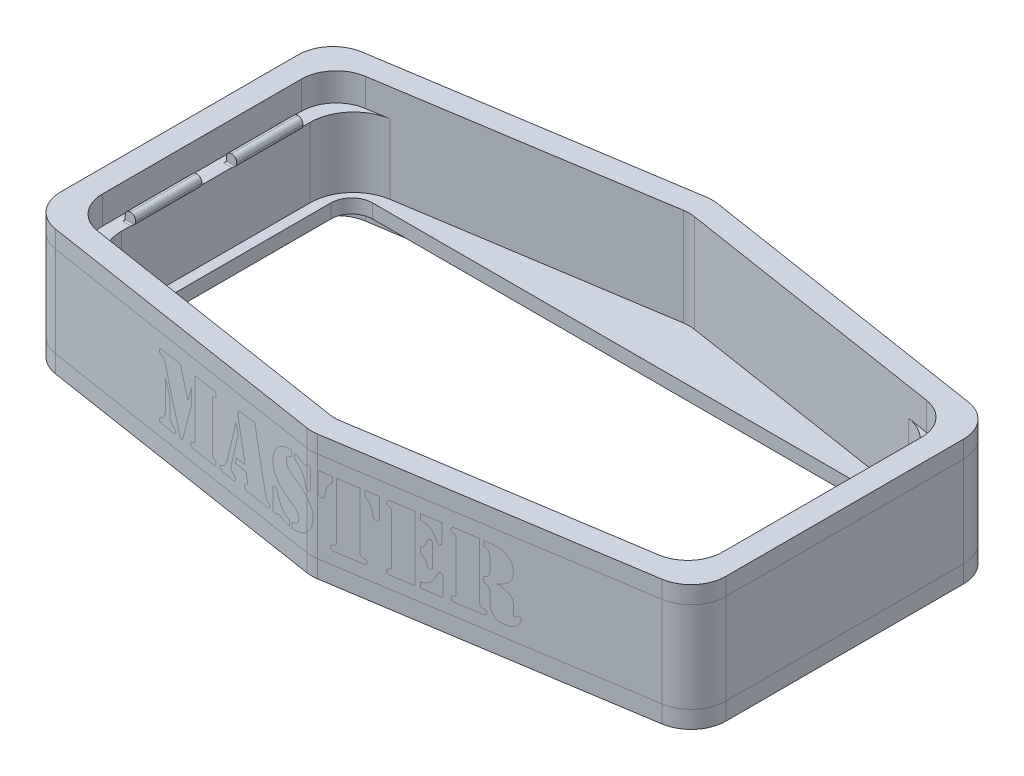
SolidWorks part; units mm, degrees
ref_plane "Front" through (0, 0, 0) normal (0, 0, 1) x (1, 0, 0)
ref_plane "Top" through (0, 0, 0) normal (0, 1, 0) x (1, 0, 0)
ref_plane "Right" through (0, 0, 0) normal (1, 0, 0) x (0, 0, -1)
sketch "Sketch1" plane through (0, 0, 0) normal (0, 1, 0) x (1, 0, 0)
  line L0 (-22.352, 9.2075) -> (0, 12.7) construction
  line L1 (-22.352, -12.7) -> (22.352, -12.7) construction
  line L2 (-22.352, -12.7) -> (-22.352, 12.7) construction
  line L3 (-22.352, 12.7) -> (22.352, 12.7) construction
  line L4 (22.352, -12.7) -> (22.352, 12.7) construction
  line L5 (-22.352, -12.7) -> (22.352, 12.7) construction
  line L6 (-22.352, 12.7) -> (22.352, -12.7) construction
  line L7 (-22.352, -9.2075) -> (22.352, -9.2075) construction
  line L8 (-22.352, -9.2075) -> (-22.352, 9.2075) construction
  line L9 (-22.352, 9.2075) -> (22.352, 9.2075) construction
  line L10 (22.352, -9.2075) -> (22.352, 9.2075) construction
  line L11 (-22.352, -9.2075) -> (22.352, 9.2075) construction
  line L12 (-22.352, 9.2075) -> (22.352, -9.2075) construction
  line L13 (0, 12.7) -> (22.352, 9.2075) construction
  line L14 (22.352, 9.2075) -> (22.352, -9.2075) construction
  line L15 (22.352, -9.2075) -> (0, -12.7) construction
  line L16 (0, -12.7) -> (-22.352, -9.2075) construction
  line L17 (-22.352, -9.2075) -> (-22.352, 9.2075) construction
  line L18 (-22.606, 9.4249) -> (0, 12.9571)
  line L19 (0, 12.9571) -> (22.606, 9.4249)
  line L20 (22.606, 9.4249) -> (22.606, -9.4249)
  line L21 (22.606, -9.4249) -> (0, -12.9571)
  line L22 (0, -12.9571) -> (-22.606, -9.4249)
  line L23 (-22.606, -9.4249) -> (-22.606, 9.4249)
  line L24 (-24.257, 10.838) -> (0, 14.6281)
  line L25 (0, 14.6281) -> (24.257, 10.838)
  line L26 (24.257, 10.838) -> (24.257, -10.838)
  line L27 (24.257, -10.838) -> (0, -14.6281)
  line L28 (0, -14.6281) -> (-24.257, -10.838)
  line L29 (-24.257, -10.838) -> (-24.257, 10.838)
  point P0 (0, 0)
  point P6 (0, 0)
  dimension "D1" = 25.4
  dimension "D2" = 18.415
  dimension "D3" = 44.704
  dimension "D4" = 0.254
  dimension "D5" = 1.651
extrude "Boss-Extrude1" add sketch "Sketch1" along normal blind 9.144
fillet "Fillet1" radius 2.54 12 edges at (0, 4.572, -14.6281) (0, 4.572, 12.9571) (0, 4.572, 14.6281) (0, 4.572, -12.9571) (22.606, 4.572, -9.4249) (22.606, 4.572, 9.4249) (-22.606, 4.572, 9.4249) (-22.606, 4.572, -9.4249) (-24.257, 4.572, -10.838) (24.257, 4.572, -10.838) (24.257, 4.572, 10.838) (-24.257, 4.572, 10.838)
ref_plane "Plane1" through (0, 1.524, 0) normal (0, -1, 0) x (-1, 0, 0)
sketch "Sketch2" plane through (0, 1.524, 0) normal (0, -1, 0) x (-1, 0, 0)
  line L0 (-22.606, -7.251) -> (-22.606, 7.251) construction
  line L1 (-19.304, 9.144) -> (19.304, 9.144)
  line L2 (-20.828, 7.62) -> (-20.828, -7.62)
  line L3 (-19.304, -9.144) -> (19.304, -9.144)
  line L4 (20.828, 7.62) -> (20.828, -7.62)
  line L5 (-0.3921, -12.8958) -> (-20.4581, -9.7605) construction
  line L6 (20.4581, -9.7605) -> (0.3921, -12.8958) construction
  line L7 (22.606, 7.251) -> (22.606, -7.251) construction
  line L8 (0.3921, 12.8958) -> (20.4581, 9.7605) construction
  line L9 (-20.4581, 9.7605) -> (-0.3921, 12.8958) construction
  line L10 (-22.606, -7.251) -> (-22.606, 7.251)
  line L11 (-0.3921, -12.8958) -> (-20.4581, -9.7605)
  line L12 (20.4581, -9.7605) -> (0.3921, -12.8958)
  line L13 (22.606, 7.251) -> (22.606, -7.251)
  line L14 (0.3921, 12.8958) -> (20.4581, 9.7605)
  line L15 (-20.4581, 9.7605) -> (-0.3921, 12.8958)
  arc A0 (-20.828, 7.62) -> (-19.304, 9.144) centre (-19.304, 7.62) cw
  arc A1 (19.304, 9.144) -> (20.828, 7.62) centre (19.304, 7.62) cw
  arc A2 (20.828, -7.62) -> (19.304, -9.144) centre (19.304, -7.62) cw
  arc A3 (-20.828, -7.62) -> (-19.304, -9.144) centre (-19.304, -7.62) ccw
  arc A4 (-20.4581, 9.7605) -> (-22.606, 7.251) centre (-20.066, 7.251) ccw construction
  arc A5 (-22.606, -7.251) -> (-20.4581, -9.7605) centre (-20.066, -7.251) ccw construction
  arc A6 (-0.3921, -12.8958) -> (0.3921, -12.8958) centre (0, -10.3863) ccw construction
  arc A7 (20.4581, -9.7605) -> (22.606, -7.251) centre (20.066, -7.251) ccw construction
  arc A8 (22.606, 7.251) -> (20.4581, 9.7605) centre (20.066, 7.251) ccw construction
  arc A9 (0.3921, 12.8958) -> (-0.3921, 12.8958) centre (0, 10.3863) ccw construction
  arc A10 (-20.4581, 9.7605) -> (-22.606, 7.251) centre (-20.066, 7.251) ccw
  arc A11 (-22.606, -7.251) -> (-20.4581, -9.7605) centre (-20.066, -7.251) ccw
  arc A12 (-0.3921, -12.8958) -> (0.3921, -12.8958) centre (0, -10.3863) ccw
  arc A13 (20.4581, -9.7605) -> (22.606, -7.251) centre (20.066, -7.251) ccw
  arc A14 (22.606, 7.251) -> (20.4581, 9.7605) centre (20.066, 7.251) ccw
  arc A15 (0.3921, 12.8958) -> (-0.3921, 12.8958) centre (0, 10.3863) ccw
  point P1 (0, 0)
  dimension "D3" = 1.524
  dimension "D1" = 41.656
  dimension "D2" = 18.288
  dimension "D4" = 20.828
  dimension "D5" = 9.144
extrude "Boss-Extrude2" add sketch "Sketch2" along normal mid plane 1.016
sketch "Sketch3" plane through (0, 2.032, 0) normal (0, 1, 0) x (1, 0, 0)
  line L0 (21.59, 6.8662) -> (21.59, -6.8662)
  line L1 (-21.59, 6.8662) -> (-21.59, -6.8662)
  line L2 (-20.4581, 9.7605) -> (-0.3921, 12.8958) construction
  line L3 (-20.4581, -9.7605) -> (-0.3921, -12.8958) construction
  line L4 (0.3921, -12.8958) -> (20.4581, -9.7605) construction
  line L5 (0.3921, 12.8958) -> (20.4581, 9.7605) construction
  line L6 (-0.3921, -12.8958) -> (-20.4581, -9.7605) construction
  line L7 (-22.606, -7.251) -> (-22.606, 7.251) construction
  line L8 (22.606, 7.251) -> (22.606, -7.251) construction
  line L9 (-0.3921, 12.8958) -> (-20.4581, 9.7605) construction
  line L10 (20.4581, 9.7605) -> (0.3921, 12.8958) construction
  line L11 (22.606, -7.251) -> (22.606, 7.251) construction
  line L12 (-18.9051, 10.0032) -> (-20.4581, 9.7605)
  line L13 (-18.9051, -10.0032) -> (-20.4581, -9.7605)
  line L14 (18.9051, -10.0032) -> (20.4581, -9.7605)
  line L15 (20.4581, 9.7605) -> (18.9051, 10.0032)
  line L16 (22.606, -7.251) -> (22.606, 7.251)
  line L17 (-22.606, 7.251) -> (-22.606, -7.251) construction
  line L18 (-22.606, 7.251) -> (-22.606, -7.251)
  arc A0 (-21.59, 6.8662) -> (-18.9051, 10.0032) centre (-18.415, 6.8662) cw
  arc A1 (-21.59, -6.8662) -> (-18.9051, -10.0032) centre (-18.415, -6.8662) ccw
  arc A2 (21.59, -6.8662) -> (18.9051, -10.0032) centre (18.415, -6.8662) cw
  arc A3 (21.59, 6.8662) -> (18.9051, 10.0032) centre (18.415, 6.8662) ccw
  arc A4 (22.606, 7.251) -> (20.4581, 9.7605) centre (20.066, 7.251) ccw construction
  arc A5 (20.4581, -9.7605) -> (22.606, -7.251) centre (20.066, -7.251) ccw construction
  arc A6 (-22.606, -7.251) -> (-20.4581, -9.7605) centre (-20.066, -7.251) ccw construction
  arc A7 (-20.4581, 9.7605) -> (-22.606, 7.251) centre (-20.066, 7.251) ccw construction
  arc A8 (22.606, 7.251) -> (20.4581, 9.7605) centre (20.066, 7.251) ccw
  arc A9 (20.4581, -9.7605) -> (22.606, -7.251) centre (20.066, -7.251) ccw
  arc A10 (-22.606, -7.251) -> (-20.4581, -9.7605) centre (-20.066, -7.251) ccw
  arc A11 (-20.4581, 9.7605) -> (-22.606, 7.251) centre (-20.066, 7.251) ccw
  dimension "D3" = 3.175
  dimension "D1" = 1.016
  dimension "D2" = 1.016
extrude "Boss-Extrude3" add sketch "Sketch3" along normal blind 5.08
sketch "Sketch4" plane through (0, 7.112, 0) normal (0, 1, 0) x (1, 0, 0)
  line L1 (22.098, 6.096) -> (21.336, 6.096)
  line L2 (22.098, 6.096) -> (22.098, 1.27)
  line L3 (22.098, 1.27) -> (21.336, 1.27)
  line L4 (21.336, 6.096) -> (21.336, 1.27)
  line L5 (22.098, -1.27) -> (21.336, -1.27)
  line L6 (22.098, -1.27) -> (22.098, -6.096)
  line L7 (22.098, -6.096) -> (21.336, -6.096)
  line L8 (21.336, -1.27) -> (21.336, -6.096)
  line L9 (-22.098, -6.096) -> (-21.336, -6.096)
  line L10 (-22.098, -6.096) -> (-22.098, -1.27)
  line L11 (-22.098, -1.27) -> (-21.336, -1.27)
  line L12 (-21.336, -6.096) -> (-21.336, -1.27)
  line L13 (-21.336, 1.27) -> (-22.098, 1.27)
  line L14 (-21.336, 1.27) -> (-21.336, 6.096)
  line L15 (-21.336, 6.096) -> (-22.098, 6.096)
  line L16 (-22.098, 1.27) -> (-22.098, 6.096)
  point P16 (-21.717, -1.27)
  dimension "D1" = 4.826
  dimension "D2" = 2.54
  dimension "D3" = 1.27
  dimension "D4" = 0.762
  dimension "D5" = 21.336
  dimension "D6" = 21.336
extrude "Boss-Extrude4" add sketch "Sketch4" along normal blind 0.762
fillet "Fillet2" radius 0.381 12 edges at (-22.098, 7.874, 3.683) (-21.336, 7.874, 3.683) (-21.336, 7.112, 3.683) (-21.336, 7.112, -3.683) (-21.336, 7.874, -3.683) (-22.098, 7.874, -3.683) (22.098, 7.874, 3.683) (21.336, 7.874, 3.683) (21.336, 7.112, 3.683) (22.098, 7.874, -3.683) (21.336, 7.874, -3.683) (21.336, 7.112, -3.683)
fillet "Fillet3" radius 0.1016 12 edges at (21.844, 7.112, -6.096) (22.098, 7.112, -3.683) (21.844, 7.112, -1.27) (21.844, 7.112, 1.27) (22.098, 7.112, 3.683) (21.844, 7.112, 6.096) (-21.844, 7.112, 6.096) (-22.098, 7.112, 3.683) (-21.844, 7.112, 1.27) (-21.844, 7.112, -6.096) (-22.098, 7.112, -3.683) (-21.844, 7.112, -1.27)
sketch "Sketch5" plane through (0, 0, 0) normal (0, 0, 1) x (1, 0, 0)
  line L0 (-24.257, 1.27) -> (24.257, 1.27)
  line L1 (24.257, 7.874) -> (-24.257, 7.874)
  line L2 (-22.1091, 0) -> (-0.3921, 0) construction
  line L3 (-22.1091, 9.144) -> (-0.3921, 9.144) construction
  line L4 (-24.257, 0) -> (-24.257, 9.144) construction
  line L5 (24.257, 9.144) -> (24.257, 0) construction
  dimension "D1" = 1.27
  dimension "D2" = 1.27
split line "Split Line1"
ref_plane "Plane2" through (0, 0, 14.5973) normal (0, 0, 1) x (1, 0, 0)
sketch "Sketch6" plane through (0, 0, 14.5973) normal (0, 0, 1) x (1, 0, 0)
  line L0 (-24.257, 2.159) -> (24.257, 2.159) construction
  line L1 (-24.257, 1.27) -> (-24.257, 7.874) construction
  line L2 (24.257, 7.874) -> (24.257, 1.27) construction
  line L3 (-22.1091, 0) -> (-0.3921, 0) construction
  text T0 "Master" font "Stencil" height 4.699
  dimension "D1" = 2.159
wrap "Wrap1" sketch "Sketch6" wrap type scribe source sketch "Sketch6"
